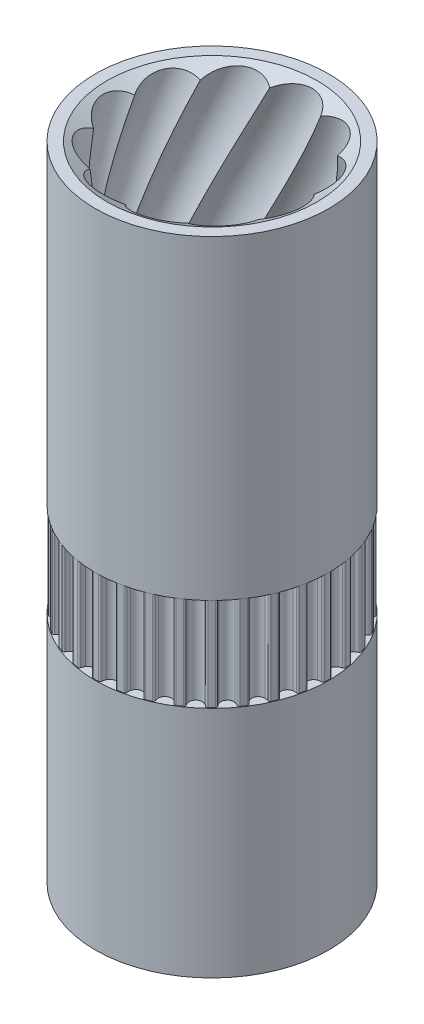
SolidWorks part; units mm, degrees
ref_plane "Front Plane" through (0, 0, 0) normal (0, 0, 1) x (1, 0, 0)
ref_plane "Top Plane" through (0, 0, 0) normal (0, 1, 0) x (1, 0, 0)
ref_plane "Right Plane" through (0, 0, 0) normal (1, 0, 0) x (0, 0, -1)
sketch "Sketch1" plane through (0, 0, 0) normal (0, 1, 0) x (1, 0, 0)
  circle A0 centre (0, 0) radius 10
  dimension "D1" = 20
ref_plane "Plane1" through (0, 0, 0) normal (0, 1, 0) x (1, 0, 0)
extrude "Boss-Extrude1" add sketch "Sketch1" along normal blind 55
sketch "Sketch2" plane through (0, 0, 0) normal (0, 1, 0) x (1, 0, 0)
  circle A0 centre (0, 0) radius 7.5
  dimension "D1" = 15
extrude "Cut-Extrude1" cut sketch "Sketch2" along normal through all
sketch "Sketch4" plane through (0, 0, 0) normal (0, 1, 0) x (1, 0, 0)
  circle A0 centre (0, 0) radius 5.5
  dimension "D1" = 11
sketch "Sketch5" plane through (0, 0, 0) normal (0, 1, 0) x (1, 0, 0)
  circle A2 centre (0, 0) radius 7.5
  circle A3 centre (0, 0) radius 7.5
  dimension "D1" = 0
loft "Cut-Loft1" cut profiles "Sketch5", "Sketch4" connector at (-0.5776, 0, 7.4777) connector at (0, 0, 5.5)
sketch "Sketch6" plane through (0, 0, 0) normal (0, 1, 0) x (1, 0, 0)
  circle A3 centre (0, 0) radius 7.5
  dimension "D1" = 15
curve "Helix/Spiral1" pitch 100 height 100 radius 7.5 left hand yes centre (0, 0, 0) axis (0, 1, 0) start towards (0, 0, 1)
sketch "Sketch7" plane through (0, 0, 0) normal (0, 1, 0) x (1, 0, 0)
  circle A33 centre (0, 0) radius 6 construction
  circle A34 centre (0, 6) radius 2.5
  dimension "D1" = 12
  dimension "D2" = 5
sweep "Cut-Sweep1" cut profiles "Sketch7" path "Helix/Spiral1" align with end faces yes
ref_plane "Plane2" through (0, 20, 0) normal (0, 1, 0) x (1, 0, 0)
ref_axis "Axis1" through (0, 55, 0) along (0, -1, 0)
pattern_circular "CirPattern2" count 11 over 360 about axis through (0, 55, 0) along (0, -1, 0) of "Cut-Sweep1"
sketch "Sketch10" plane through (0, 20, 0) normal (0, 1, 0) x (1, 0, 0)
  line L0 (0, 0) -> (0, 9.93) construction
  line L1 (0.9644, 9.5437) -> (0, 0) construction
  line L2 (1.3827, 9.7422) -> (0, 0) construction
  line L4 (0, 9.93) -> (0, 10.56)
  line L8 (1.9865, 9.7293) -> (2.1125, 10.3465)
  arc A0 (0, 9.93) -> (0.2519, 9.9268) centre (0, 0) cw
  arc A1 (0.2519, 9.9268) -> (0.3979, 9.785) centre (0.2481, 9.7769) cw
  arc A2 (0.3979, 9.785) -> (0.4577, 9.4944) centre (1.3964, 9.839) ccw
  arc A3 (0.4577, 9.4944) -> (1.4509, 9.394) centre (0.9787, 9.6857) ccw
  circle A4 centre (0, 0) radius 9.93 construction
  arc A5 (1.5676, 9.6668) -> (1.4509, 9.394) centre (0.6001, 9.9195) cw
  arc A6 (1.739, 9.7765) -> (1.5676, 9.6668) centre (1.7128, 9.6289) ccw
  arc A7 (1.9865, 9.7293) -> (1.739, 9.7765) centre (0, 0) ccw
  arc A8 (2.1125, 10.3465) -> (0, 10.56) centre (0, 0) ccw
  arc A9 (-1.4839, -10.4552) -> (-1.0616, -10.5065) centre (0, 0) ccw
  circle A10 centre (0, 0) radius 9.18 construction
  point P15 (0.9983, 9.8797)
  point P17 (1.3954, 9.8315)
  point P25 (0.5996, 9.9119)
  dimension "D2" = 0.75
  dimension "R1" = 0.15
  dimension "D3" = 1
  dimension "OD" = 19.86
  dimension "R2" = 1
  dimension "R3" = 0.555
  dimension "D1" = 1.38
  dimension "b" = 0.4
extrude "Cut-Extrude3" cut sketch "Sketch10" along normal blind 8 contours A5 A3 A2 A1 A0 L4 A8 L8 A7 A6
pattern_circular "CirPattern1" count 32 over 360 about axis through (0, 55, 0) along (0, -1, 0) of "Cut-Extrude3"
chamfer "Chamfer1" [suppressed] distance 1 angle 45
sketch "Sketch11" plane through (0, 0, 0) normal (1, 0, 0) x (0, 0, -1)
  line L0 (-9, 55) -> (0, 55)
  line L1 (10, 55) -> (-10, 55) construction
  line L2 (0, 55) -> (0, 49.8038)
  line L3 (0, 55) -> (0, 0) construction
  line L4 (0, 49.8038) -> (-9, 55)
  dimension "D1" = 1
  dimension "D2" = 30
revolve "Cut-Revolve1" cut sketch "Sketch11" angle 360 about L2
